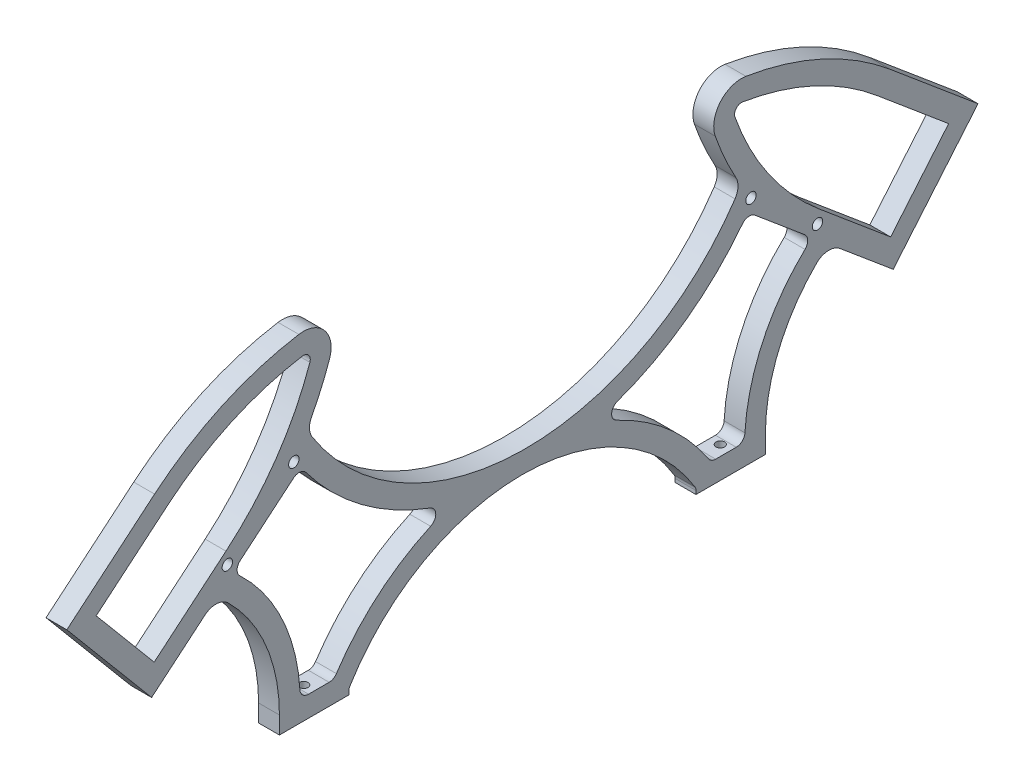
SolidWorks part; units mm, degrees
material "1060 Alloy"
ref_plane "Front Plane" through (0, 0, 0) normal (0, 0, 1) x (1, 0, 0)
ref_plane "Top Plane" through (0, 0, 0) normal (0, 1, 0) x (1, 0, 0)
ref_plane "Right Plane" through (0, 0, 0) normal (1, 0, 0) x (0, 0, -1)
sketch "Sketch1" plane through (0, 0, 0) normal (1, 0, 0) x (0, 0, -1)
  line L0 (0, 0) -> (0, 5)
  line L1 (-60.4789, 57.5279) -> (-34.1246, 26.1201) construction
  line L2 (-60.4789, 57.5279) -> (0.8047, 108.9509) construction
  line L3 (-34.1246, 26.1201) -> (27.1589, 77.5431) construction
  line L4 (-57.0184, 56.5154) -> (-36.4492, 32.0019) construction
  line L5 (0.8047, 108.9509) -> (27.1589, 77.5431) construction
  line L6 (20, 1) -> (20, 0)
  line L7 (0, 0) -> (20, 0)
  line L8 (-36.4492, 32.0019) -> (-13.4679, 51.2856) construction
  line L9 (-34.0371, 75.799) -> (-57.0184, 56.5154) construction
  line L10 (153.5041, 47.339) -> (134.9361, 62.9194)
  line L11 (-35.9655, 78.0971) -> (-61.2449, 56.8851)
  line L12 (6.1233, 63.8084) -> (-13.5041, 47.339)
  line L13 (134.009, 6) -> (124.3139, 6)
  line L14 (200.4789, 57.5279) -> (174.1246, 26.1201) construction
  line L15 (200.4789, 57.5279) -> (139.1953, 108.9509) construction
  line L16 (174.1246, 26.1201) -> (112.8411, 77.5431) construction
  line L17 (139.1953, 108.9509) -> (112.8411, 77.5431) construction
  line L18 (176.4492, 32.0019) -> (197.0184, 56.5154) construction
  line L19 (197.0184, 56.5154) -> (174.0371, 75.799) construction
  line L20 (153.4679, 51.2856) -> (176.4492, 32.0019) construction
  line L21 (186.7338, 44.2587) -> (126.9824, 94.3961) construction
  line L22 (-46.7338, 44.2587) -> (13.0176, 94.3961) construction
  line L23 (15.6861, 6) -> (5.991, 6)
  line L24 (161.4981, 40.6312) -> (176.819, 27.7755)
  line L25 (176.819, 27.7755) -> (201.2449, 56.8851)
  line L26 (201.2449, 56.8851) -> (175.9655, 78.0971)
  line L27 (-61.2449, 56.8851) -> (-36.819, 27.7755)
  line L28 (140, 0) -> (140, 5)
  line L29 (-36.819, 27.7755) -> (-21.4981, 40.6312)
  line L30 (-36.819, 27.7755) -> (-11.5395, 48.9874) construction
  line L31 (155.3963, 53.5837) -> (176.0795, 36.2284)
  line L32 (176.0795, 36.2284) -> (192.792, 56.1456)
  line L33 (192.792, 56.1456) -> (172.1088, 73.5009)
  line L34 (109.9256, 30) -> (27.8477, 30) construction
  line L35 (109.9256, 36) -> (27.8477, 36) construction
  line L37 (-32.1088, 73.5009) -> (-52.792, 56.1456)
  line L38 (-52.792, 56.1456) -> (-36.0795, 36.2284)
  line L39 (-36.0795, 36.2284) -> (-15.3963, 53.5837)
  line L40 (151.5395, 48.9874) -> (176.819, 27.7755) construction
  line L43 (140, 0) -> (120, 0)
  line L56 (120, 1) -> (120, 0)
  line L63 (174.6584, 98) -> (-14.1241, 98) construction
  circle A0 centre (-15, 50) radius 1.5
  circle A1 centre (155, 50) radius 1.5
  circle A2 centre (4.1511, 66.0697) radius 1.5
  circle A3 centre (135.8489, 66.0697) radius 1.5
  circle A4 centre (155, 50) radius 3 construction
  circle A5 centre (135.8489, 66.0697) radius 3 construction
  circle A6 centre (-15, 50) radius 3 construction
  circle A7 centre (4.1511, 66.0697) radius 3 construction
  arc A8 (175.9655, 78.0971) -> (134.3963, 97.1498) centre (120.5397, 12.0432) ccw
  arc A9 (134.3963, 97.1498) -> (125.5579, 86.6166) centre (133.1107, 89.2538) ccw
  arc A10 (125.5579, 86.6166) -> (131.4873, 73.3496) centre (206.9654, 115.0414) ccw
  arc A11 (9.2334, 74.6819) -> (14.4421, 86.6166) centre (-66.9654, 115.0414) ccw
  arc A12 (-13.4679, 51.2856) -> (11.6098, 87.6055) centre (-66.9654, 115.0414) ccw construction
  arc A13 (11.6098, 87.6055) -> (6.0858, 94.1888) centre (6.8893, 89.2538) ccw construction
  arc A14 (6.0858, 94.1888) -> (-34.0371, 75.799) centre (19.4603, 12.0432) ccw construction
  arc A15 (174.0371, 75.799) -> (133.9142, 94.1888) centre (120.5397, 12.0432) ccw construction
  arc A16 (133.9142, 94.1888) -> (128.3902, 87.6055) centre (133.1107, 89.2538) ccw construction
  arc A17 (128.3902, 87.6055) -> (153.4679, 51.2856) centre (206.9654, 115.0414) ccw construction
  arc A18 (14.4421, 86.6166) -> (5.6037, 97.1498) centre (6.8893, 89.2538) ccw
  arc A19 (5.6037, 97.1498) -> (-35.9655, 78.0971) centre (19.4603, 12.0432) ccw
  arc A20 (172.1088, 73.5009) -> (133.4321, 91.2278) centre (120.5397, 12.0432) ccw
  arc A21 (133.4321, 91.2278) -> (131.2225, 88.5945) centre (133.1107, 89.2538) ccw
  arc A22 (131.2225, 88.5945) -> (155.3963, 53.5837) centre (206.9654, 115.0414) ccw
  arc A23 (-11.5395, 48.9874) -> (14.4421, 86.6166) centre (-66.9654, 115.0414) ccw construction
  arc A24 (124.3139, 6) -> (90.7471, 32.5533) centre (70, -28.1667) ccw
  arc A25 (50.0021, 32.8042) -> (6.1233, 63.8084) centre (70.8436, 108.8521) cw
  arc A26 (20, 1) -> (20.2908, 2.0386) centre (22, 1) cw
  arc A27 (-15.3963, 53.5837) -> (8.7775, 88.5945) centre (-66.9654, 115.0414) ccw
  arc A28 (8.7775, 88.5945) -> (6.5679, 91.2278) centre (6.8893, 89.2538) ccw
  arc A29 (6.5679, 91.2278) -> (-32.1088, 73.5009) centre (19.4603, 12.0432) ccw
  arc A30 (125.5579, 86.6166) -> (151.5395, 48.9874) centre (206.9654, 115.0414) ccw construction
  arc A31 (134.9361, 62.9194) -> (90.7471, 32.5533) centre (70.8436, 108.8521) cw
  arc A32 (140, 5) -> (154.7699, 40.3576) centre (189.7062, 5) cw
  arc A33 (161.4981, 40.6312) -> (154.7699, 40.3576) centre (158.2842, 36.801) ccw
  arc A34 (0, 5) -> (-14.7699, 40.3576) centre (-49.7062, 5) ccw
  arc A35 (-21.4981, 40.6312) -> (-14.7699, 40.3576) centre (-18.2842, 36.801) cw
  arc A36 (131.4873, 73.3496) -> (131.2569, 68.1377) centre (127.1106, 70.932) cw
  arc A37 (9.2334, 74.6819) -> (9.4375, 69.6512) centre (13.6519, 72.3416) ccw
  arc A38 (131.2569, 68.1377) -> (9.4375, 69.6512) centre (70.8436, 108.8521) cw
  arc A39 (153.5041, 47.339) -> (134.009, 6) centre (189.7062, 5) ccw
  arc A40 (-13.5041, 47.339) -> (5.991, 6) centre (-49.7062, 5) cw
  arc A41 (50.0021, 32.8042) -> (15.6861, 6) centre (70, -28.1667) ccw
  arc A44 (120, 1) -> (119.7092, 2.0386) centre (118, 1) ccw
  arc A45 (119.7092, 2.0386) -> (20.2908, 2.0386) centre (70, -28.1667) ccw
  dimension "D1" = 3
  dimension "D8" = 5
  dimension "D11" = 50
  dimension "D12" = 15
  dimension "D14" = 25
  dimension "D16" = 2
  dimension "D17" = 6
  dimension "D21" = 40
  dimension "D22" = 35
  dimension "D23" = 80
  dimension "D24" = 3
  dimension "D18" = 6
  dimension "D29" = 50
  dimension "D25" = 5
  dimension "D28" = 6
  dimension "D36" = 5
  dimension "D37" = 20
  dimension "D38" = 10
  dimension "D39" = 8
  dimension "D40" = 10
  dimension "D45" = 6
  dimension "D46" = 6
  dimension "D47" = 6
  dimension "D48" = 6
  dimension "D49" = 30
  dimension "D56" = 2
  dimension "D4" = 25
  dimension "D6" = 28
  dimension "D7" = 15
  dimension "D9" = 20
  dimension "D10" = 100
  dimension "D13" = 1
  dimension "D15" = 40
  dimension "D19" = 30
  dimension "D20" = 30
  dimension "D26" = 3
  dimension "D27" = 2
  dimension "D30" = 3
  dimension "D31" = 3
  dimension "D32" = 98
  dimension "D33" = 3
  dimension "D34" = 6
  dimension "D35" = 3
  dimension "D41" = 3
  dimension "D42" = 3
  dimension "D43" = 6
  dimension "D44" = 6
extrude "Boss-Extrude1" add sketch "Sketch1" along normal blind 6
hole_wizard "Tap Drill for M3 Tap1" positions "Sketch3" profile "Sketch2" hole size "M3" standard "ISO"
sketch "Sketch3" plane through (0, 0, 0) normal (0, -1, 0) x (-1, 0, 0)
  line L0 (-6, 20) -> (0, 20) construction
  line L1 (0, 0) -> (0, 20) construction
  line L2 (-6, 120) -> (0, 120) construction
  point P0 (-3, 10)
  point P2 (-3, 130)
  dimension "D1" = 10
  dimension "D2" = 3
  dimension "D3" = 10
sketch "Sketch2" plane through (3, 0, -10) normal (1, 0, 0) x (0, 0, -1)
  line L0 (0, 0) -> (0, 10.7511)
  line L1 (0, 10.7511) -> (1.25, 10)
  line L2 (1.25, 10) -> (1.25, 0)
  line L5 (1.25, 0) -> (0, 0)
  line L10 (0, 10.7511) -> (-1.25, 10) construction
  line L11 (0, -6.35) -> (0, 107.95) construction
  dimension "Hole Dia." = 2.5
  dimension "Hole Depth" = 10
  dimension "Drill Angle" = 118
fillet "Fillet1" radius 2.5 10 edges at (3, 6, -15.6861) (3, 6, -5.991) (3, 47.339, 13.5041) (3, 63.8084, -6.1233) (3, 47.339, -153.5041) (3, 6, -134.009) (3, 62.9194, -134.9361) (3, 32.8042, -50.0021) (3, 6, -124.3139) (3, 32.5533, -90.7471)
equation "\"ˇ35\"=76.24"
